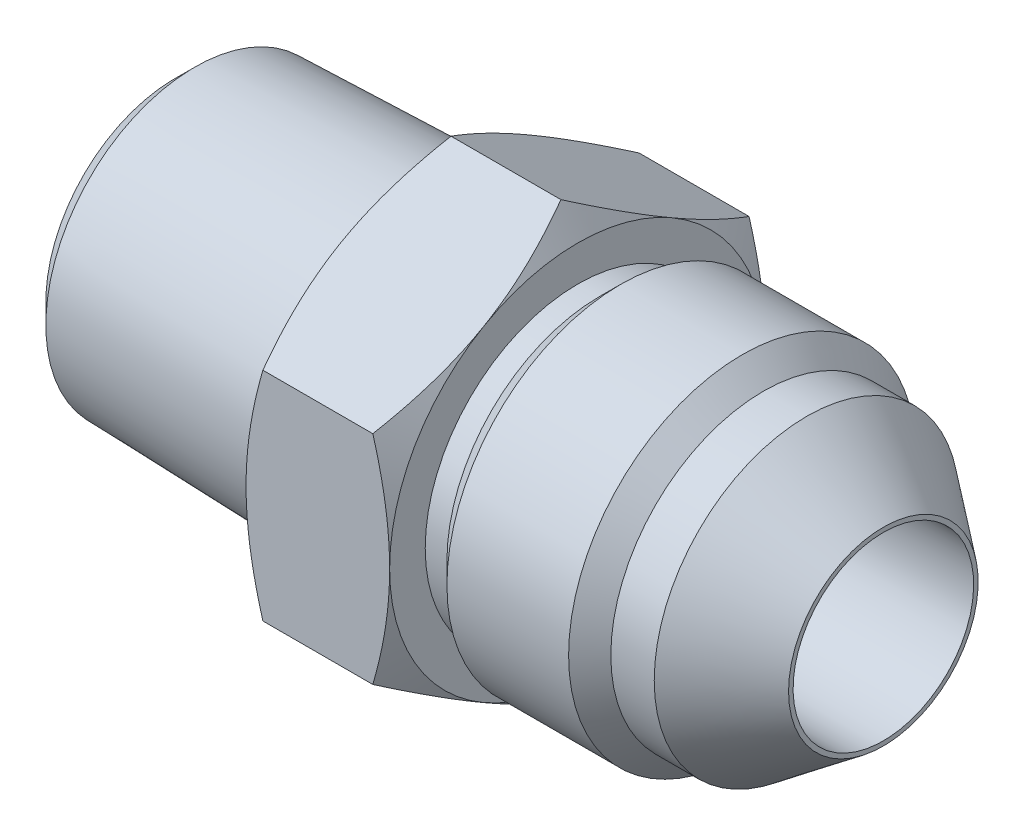
SolidWorks part; units mm, degrees
ref_plane "Front" through (0, 0, 0) normal (0, 0, 1) x (1, 0, 0)
ref_plane "Top" through (0, 0, 0) normal (0, 1, 0) x (1, 0, 0)
ref_plane "Right" through (0, 0, 0) normal (1, 0, 0) x (0, 0, -1)
sketch "Sketch6" plane through (0, 0, 0) normal (0, 0, 1) x (1, 0, 0)
  line L0 (-5.207, 8.5725) -> (-5.207, -8.5725) construction
  line L1 (19.431, 9.525) -> (19.431, -9.525) construction
  line L2 (-19.431, 0) -> (19.431, 0)
  line L4 (-19.431, 0) -> (-19.431, 9.525)
  line L5 (-19.431, 9.525) -> (19.431, 9.525)
  line L6 (19.431, 0) -> (19.431, 9.525)
  line L7 (-19.431, 4.953) -> (-19.431, -4.953) construction
  line L8 (-5.207, 11.0808) -> (-5.207, -11.0808) construction
  line L9 (2.667, 11.0808) -> (2.667, -11.0808) construction
  point P4 (2.667, 0)
  point P6 (-5.207, 0)
  dimension "Straight Dia" = 19.05
  dimension "Length" = 38.862
  dimension "L1" = 16.764
  dimension "Pipe OD" = 17.145
  dimension "L2" = 14.224
  dimension "D1" = 9.906
  dimension "D2" = 22.1615
revolve "Revolve3" add sketch "Sketch6" angle 360 about L2
sketch "Sketch14" plane through (19.431, 0, 0) normal (-1, 0, 0) x (0, 0, 1)
  circle A1 centre (0, 0) radius 9.525
  circle A2 centre (0, 0) radius 9.525
  dimension "D1" = 0
curve "Helix/Spiral1" pitch 1.5875 height 18.3515 turns 11.56 parameters "Pitch"=1.5875
sketch "Sketch15" plane through (0, 0, 0) normal (0, 0, 1) x (1, 0, 0)
  line L0 (19.431, 9.525) -> (20.8201, 9.525)
  line L1 (20.8201, 9.525) -> (20.2247, 8.4939)
  line L2 (20.2247, 8.4939) -> (20.0263, 8.4939)
  line L3 (20.0263, 8.4939) -> (19.431, 9.525)
  line L4 (20.1255, 8.4939) -> (20.1255, 9.525) construction
  line L5 (19.7287, 9.0094) -> (20.5224, 9.0094) construction
  dimension "D1" = 60
  dimension "D2" = 0.1984
  dimension "D3" = 0.7937
sweep "Cut-Sweep1" [suppressed] cut profiles "Sketch15" path "Helix/Spiral1"
ref_plane "Plane1" through (-5.207, 0, 0) normal (1, 0, 0) x (0, 0, -1)
sketch "Sketch12" plane through (-5.207, 0, 0) normal (1, 0, 0) x (0, 0, -1)
  line L1 (0, 11.9151) -> (-10.3187, 5.9575)
  line L2 (-10.3187, 5.9575) -> (-10.3187, -5.9575)
  line L3 (-10.3187, -5.9575) -> (0, -11.9151)
  line L4 (0, -11.9151) -> (10.3187, -5.9575)
  line L5 (10.3187, -5.9575) -> (10.3187, 5.9575)
  line L6 (10.3187, 5.9575) -> (0, 11.9151)
  circle A0 centre (0, 0) radius 10.3187 construction
  dimension "Hex" = 20.6375
extrude "Extrude1" add sketch "Sketch12" along normal up to vertex (7.874 mm away) up to point (2.667, 0, 0)
sketch "Sketch7" plane through (0, 0, 0) normal (0, 0, 1) x (1, 0, 0)
  line L0 (-19.431, 0) -> (-19.431, 4.953)
  line L2 (-19.431, 4.953) -> (19.431, 4.953)
  line L4 (19.431, 0) -> (19.431, 9.525) construction
  line L11 (19.431, 4.953) -> (19.431, 0)
  line L12 (19.431, 0) -> (-19.431, 0)
  line L13 (-19.431, 4.953) -> (-19.431, -4.953) construction
  dimension "ID" = 9.906
sketch "Sketch10" plane through (0, 0, 0) normal (0, 0, 1) x (1, 0, 0)
  line L0 (-19.431, 9.525) -> (19.431, 9.525) construction
  line L1 (19.431, 9.525) -> (20.8201, 9.525) construction
  line L2 (-5.207, -8.5725) -> (-19.431, -8.1378) construction
  line L3 (2.667, 11.9151) -> (2.667, 5.9575) construction
  line L5 (0, 0) -> (-19.431, 0) construction
  line L6 (5.0157, 9.525) -> (2.667, 9.525)
  line L9 (2.667, 8.3669) -> (2.667, 9.525)
  line L21 (19.431, 9.525) -> (11.6899, 9.525)
  line L22 (11.6899, 9.525) -> (12.848, 8.3669)
  line L23 (12.848, 8.3669) -> (15.2293, 8.3669)
  line L24 (15.2293, 8.3669) -> (19.431, 5.2007)
  line L25 (19.431, 5.2007) -> (19.431, 9.525)
  line L26 (3.8576, 8.3669) -> (2.667, 8.3669)
  line L27 (5.0157, 9.525) -> (3.8576, 8.3669)
  point P5 (9.673, -9.525)
  point P9 (-13.081, -8.3319)
  dimension "D1" = 10.4013
  dimension "D2" = 37
  dimension "D3" = 2.3813
  dimension "D5" = 45
  dimension "D4" = 1.1906
  dimension "D6" = 3.175
  dimension "D7" = 0.127
  dimension "D9" = 6.35
  dimension "D8" = 1.75
revolve "Cut-Revolve6" cut sketch "Sketch10" angle 360 about L2
revolve "Cut-Revolve5" cut sketch "Sketch7" angle 360 about L12
sketch "Sketch13" plane through (0, 0, 0) normal (0, 0, 1) x (1, 0, 0)
  line L0 (-5.207, 11.9151) -> (-5.207, 10.3187)
  line L1 (-5.207, 5.9575) -> (-5.207, 11.9151) construction
  line L2 (-5.207, 10.3187) -> (-4.2854, 11.9151)
  line L3 (-4.2854, 11.9151) -> (-5.207, 11.9151)
  line L4 (1.7454, 11.9151) -> (2.667, 10.3187)
  line L5 (2.667, 11.9151) -> (2.667, 5.9575) construction
  line L6 (2.667, 10.3187) -> (2.667, 11.9151)
  line L7 (2.667, 11.9151) -> (1.7454, 11.9151)
  dimension "D2" = 30
revolve "Cut-Revolve7" cut sketch "Sketch13" angle 360 about L2
sketch "Sketch17" plane through (-19.431, 0, 0) normal (-1, 0, 0) x (0, 0, 1)
  circle A0 centre (0, 0) radius 9.525 construction
  circle A1 centre (0, 0) radius 9.525
extrude "Cut-Extrude1" cut sketch "Sketch17" against normal up to vertex (14.224 mm away) up to point (-5.207, 0, 0)
ref_plane "Plane2" through (-5.207, 0, 0) normal (1, 0, 0) x (0, 0, -1)
sketch "Sketch19" plane through (-5.207, 0, 0) normal (1, 0, 0) x (0, 0, -1)
  circle A0 centre (0, 0) radius 8.5725
extrude "Boss-Extrude1" add sketch "Sketch19" against normal up to vertex (14.224 mm away) draft 1.75 separate body up to point (-19.431, 0, 0)
sketch "Sketch20" plane through (-19.431, 0, 0) normal (1, 0, 0) x (0, 0, -1)
  circle A1 centre (0, 0) radius 8.1379
  circle A2 centre (0, 0) radius 8.1379 construction
sketch "Sketch21" plane through (0, 0, 0) normal (0, 0, 1) x (1, 0, 0)
  line L0 (-20.6341, 8.0178) -> (-19.5003, 8.0178) construction
  line L1 (-20.7728, 8.258) -> (-20.0672, 7.036) construction
  line L2 (-20.1873, 7.244) -> (-19.9471, 7.244)
  line L3 (-20.0672, 7.036) -> (-19.3617, 8.258) construction
  line L4 (-20.0672, 7.036) -> (-19.9471, 7.244) construction
  line L5 (-20.0672, 8.0178) -> (-20.0672, 8.258) construction
  line L6 (-20.7728, 8.258) -> (-19.3617, 8.258) construction
  line L7 (-20.0672, 8.1379) -> (-19.431, 8.1379) construction
  line L8 (-19.3617, 8.258) -> (-20.7034, 8.1379)
  line L9 (-20.7034, 8.1379) -> (-20.1873, 7.244)
  line L10 (-19.9471, 7.244) -> (-19.3617, 8.258)
  line L11 (-20.0672, 7.036) -> (-20.0672, 7.244) construction
  dimension "D2" = 0.2402
  dimension "D1" = 1.4111
curve "Helix/Spiral2" parameters "Pitch"=1.4111
chamfer "Chamfer1" distance 1.0583 angle 45 1 edges at (-19.431, 0, -8.1379) first distance on face at (-19.431, 0, -8.1379)
sketch "Sketch22" plane through (-5.207, 0, 0) normal (1, 0, 0) x (0, 0, -1)
  circle A1 centre (0, 0) radius 8.5725
  circle A2 centre (0, 0) radius 8.5725
  dimension "D1" = 0
sweep "Cut-Sweep2" [suppressed] cut profiles "Sketch21" path "Helix/Spiral2"
extrude "Boss-Extrude3" add sketch "Sketch22" against normal up to vertex (14.224 mm away) draft 15 up to point (-19.431, 9.525, 0)
combine bodies "Combine1" operation type add bodies to combine 173 169
sketch "Sketch23" plane through (-19.431, 0, 0) normal (-1, 0, 0) x (0, 0, 1)
  circle A2 centre (0, 0) radius 4.953
extrude "Cut-Extrude2" cut sketch "Sketch23" against normal up to vertex (14.224 mm away) up to point (-5.207, 0, 0)
other "CPoint1" parameters "Diameter"=12.7, "StubLength"=25.4
ref_axis "Axis1" through (29.431, 0, 0) along (-1, 0, 0)
equation "\"D3@Helix/Spiral1\" = \"L1@Sketch6\"+\"Pitch@Helix/Spiral1\""
equation "\"D2@Sketch15\" = \"Pitch@Helix/Spiral1\"*.125"
equation "\"D3@Sketch15\" = \"Pitch@Helix/Spiral1\"*.5"
equation "\"D3@Sketch10\" = \"Pitch@Helix/Spiral1\"*1.5"
equation "\"D1@Sketch10\" = \"ID@Sketch7\"*1.05"
equation "\"D1@Sketch21\" = \"Pitch@Helix/Spiral2\""
equation "\"D3@Helix/Spiral2\" = \"L2@Sketch6\"+\"Pitch@Helix/Spiral2\""
equation "\"D1@Chamfer1\" = \"Pitch@Helix/Spiral2\"*.75"
equation "\"D4@Sketch10\" = \"Pitch@Helix/Spiral1\"*.75"
equation "\"D6@Sketch10\" = \"Pitch@Helix/Spiral1\"*2"
equation "\"D9@Sketch10\" = \"Pitch@Helix/Spiral2\"*4.5"
equation "\"D2@Sketch6\" = \"Hex@Sketch12\"+.06"
